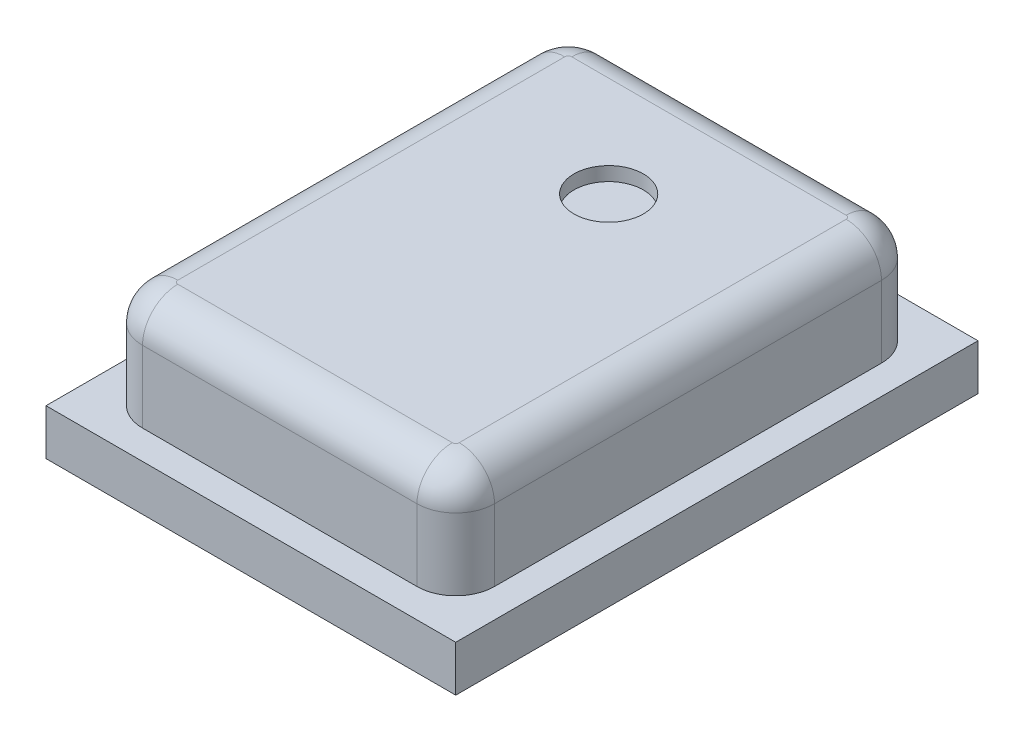
SolidWorks part; units mm, degrees
ref_plane "Front Plane" through (0, 0, 0) normal (0, 0, 1) x (1, 0, 0)
ref_plane "Top Plane" through (0, 0, 0) normal (0, 1, 0) x (1, 0, 0)
ref_plane "Right Plane" through (0, 0, 0) normal (1, 0, 0) x (0, 0, -1)
sketch "Sketch1" plane through (0, 0, 0) normal (0, 1, 0) x (1, 0, 0)
  line L1 (-1.475, 1.88) -> (1.475, 1.88)
  line L2 (-1.475, 1.88) -> (-1.475, -1.88)
  line L3 (-1.475, -1.88) -> (1.475, -1.88)
  line L4 (1.475, 1.88) -> (1.475, -1.88)
  line L5 (-1.475, 1.88) -> (1.475, -1.88) construction
  line L6 (-1.475, -1.88) -> (1.475, 1.88) construction
  point P0 (0, 0)
  dimension "D1" = 2.95
  dimension "D2" = 3.76
extrude "Boss-Extrude1" add sketch "Sketch1" along normal blind 0.33
sketch "Sketch2" plane through (0, 0.33, 0) normal (0, 1, 0) x (1, 0, 0)
  line L1 (-1.267, -1.672) -> (1.267, -1.672)
  line L2 (-1.267, -1.672) -> (-1.267, 1.672)
  line L3 (-1.267, 1.672) -> (1.267, 1.672)
  line L4 (1.267, -1.672) -> (1.267, 1.672)
  line L5 (-1.267, -1.672) -> (1.267, 1.672) construction
  line L6 (-1.267, 1.672) -> (1.267, -1.672) construction
  point P0 (0, 0)
  dimension "D1" = 2.534
  dimension "D2" = 3.344
extrude "Boss-Extrude2" add sketch "Sketch2" along normal blind 0.77
fillet "Fillet1" radius 0.254 4 edges at (0, 1.1, 1.672) (-1.267, 1.1, 0) (0, 1.1, -1.672) (1.267, 1.1, 0)
fillet "Fillet2" radius 0.279 8 edges at (-1.1926, 1.0256, 1.5976) (1.1926, 1.0256, 1.5976) (-1.1926, 1.0256, -1.5976) (1.1926, 1.0256, -1.5976) (1.267, 0.588, -1.672) (-1.267, 0.588, -1.672) (1.267, 0.588, 1.672) (-1.267, 0.588, 1.672)
sketch "Sketch3" plane through (0, 1.1, 0) normal (0, 1, 0) x (1, 0, 0)
  line L0 (1.475, 1.88) -> (-1.475, 1.88) construction
  circle A0 centre (0, 0.696) radius 0.25
  dimension "D2" = 0.5
  dimension "D1" = 1.184
extrude "Cut-Extrude1" cut sketch "Sketch3" against normal blind 0.1
